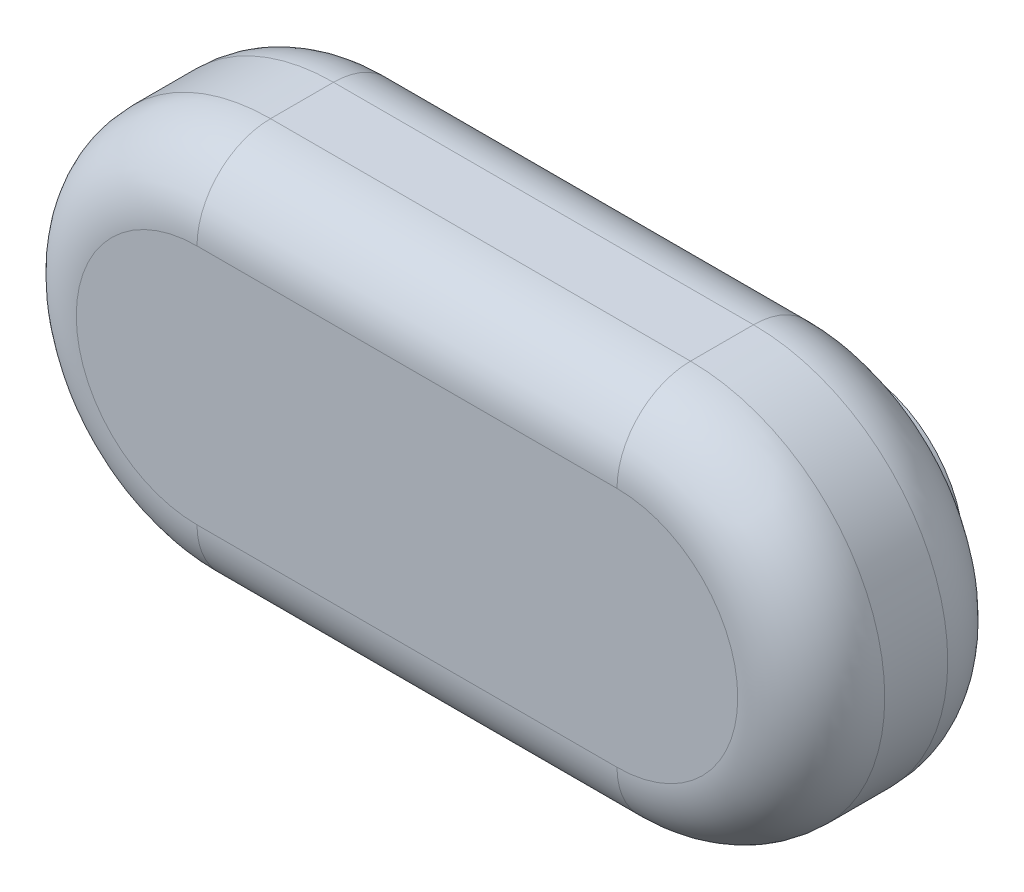
SolidWorks part; units mm, degrees
material "ABS PC"
ref_plane "Plan de face" through (0, 0, 0) normal (0, 0, 1) x (1, 0, 0)
ref_plane "Plan de dessus" through (0, 0, 0) normal (0, 1, 0) x (1, 0, 0)
ref_plane "Plan de droite" through (0, 0, 0) normal (1, 0, 0) x (0, 0, -1)
sketch "Esquisse1" plane through (0, 0, 0) normal (0, 0, 1) x (1, 0, 0)
  line L0 (-31.0423, 19.278) -> (-71.0423, 19.278)
  line L1 (-71.0423, -17.722) -> (-31.0423, -17.722)
  arc A0 (-71.0423, -17.722) -> (-71.0423, 19.278) centre (-71.0423, 0.778) cw
  arc A1 (-31.0423, 19.278) -> (-31.0423, -17.722) centre (-31.0423, 0.778) cw
  dimension "D1" = 40
  dimension "D2" = 37
extrude "Boss.-Extru.1" add sketch "Esquisse1" along normal blind 20
fillet "Congé1" radius 7 8 edges at (-51.0423, 19.278, 0) (-89.5423, 0.778, 0) (-51.0423, -17.722, 0) (-12.5423, 0.778, 0) (-89.5423, 0.778, 20) (-51.0423, -17.722, 20) (-12.5423, 0.778, 20) (-51.0423, 19.278, 20)
sketch "Esquisse2" plane through (0, 0, 0) normal (0, 0, -1) x (-1, 0, 0)
  line L1 (71.0423, -17.722) -> (31.0423, -17.722) construction
  circle A0 centre (31.0423, 0.778) radius 10
  arc A6 (31.0423, 19.278) -> (31.0423, -17.722) centre (31.0423, 0.778) ccw construction
  point P12 (12.5423, 0.778)
  dimension "D1" = 20
  dimension "D4" = 18.5
  dimension "D2" = 18.5
extrude "Boss.-Extru.2" add sketch "Esquisse2" along normal blind 3
shell "Coque1" thickness 1.5
